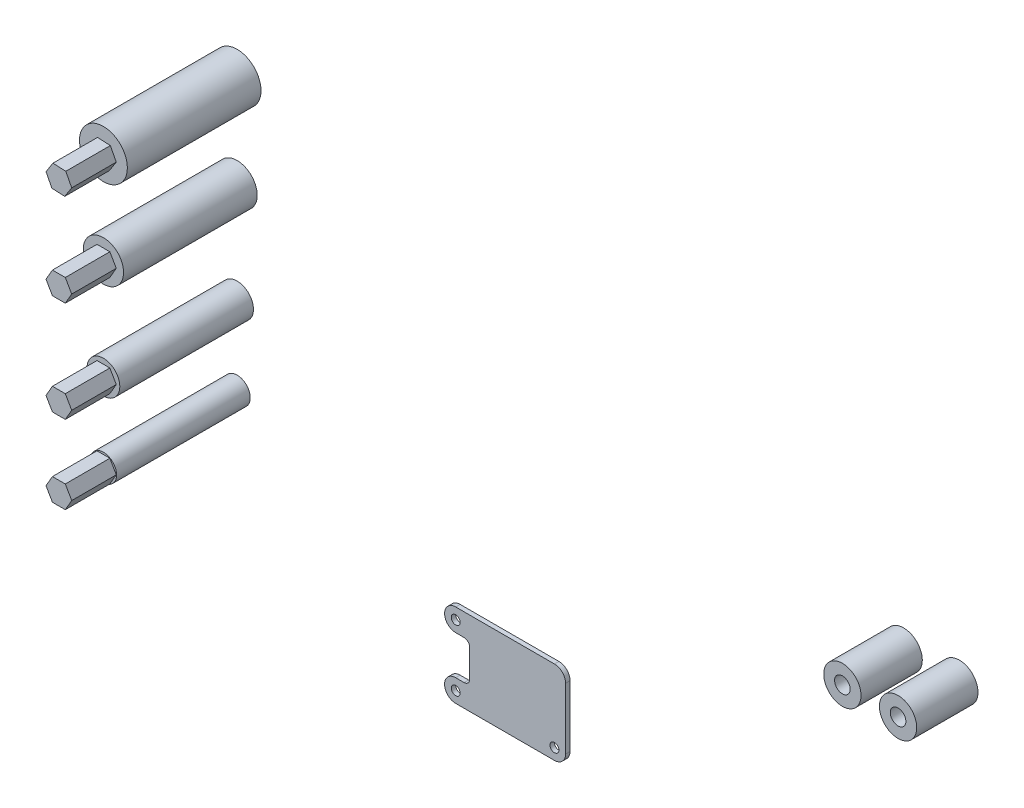
SolidWorks part; units mm, degrees
ref_plane "Front Plane" through (0, 0, 0) normal (0, 0, 1) x (1, 0, 0)
ref_plane "Top Plane" through (0, 0, 0) normal (0, 1, 0) x (1, 0, 0)
ref_plane "Right Plane" through (0, 0, 0) normal (1, 0, 0) x (0, 0, -1)
sketch "Sketch1" plane through (0, 0, 0) normal (0, 0, 1) x (1, 0, 0)
  line L0 (41.5252, 85.2495) -> (55.5016, 85.2495) construction
  line L1 (58.7537, 81.2495) -> (58.7537, 83.2495)
  line L2 (40.5252, 83.2495) -> (39.0252, 83.2495)
  line L3 (39.0252, 79.2495) -> (56.7537, 79.2495)
  line L4 (41.5252, 84.2495) -> (41.5252, 85.2495)
  line L5 (-0.0481, 105.8254) -> (0.9333, 107.5254)
  line L6 (0.9333, 107.5254) -> (-0.0481, 109.2254)
  line L7 (-0.0481, 109.2254) -> (-2.0111, 109.2254)
  line L8 (-2.0111, 109.2254) -> (-2.9926, 107.5254)
  line L9 (-2.9926, 107.5254) -> (-2.0111, 105.8254)
  line L10 (-2.0111, 105.8254) -> (-0.0481, 105.8254)
  line L11 (0.2405, 119.3642) -> (1.5107, 121.5642)
  line L12 (1.5107, 121.5642) -> (0.2405, 123.7642)
  line L13 (0.2405, 123.7642) -> (-2.2998, 123.7642)
  line L14 (-2.2998, 123.7642) -> (-3.57, 121.5642)
  line L15 (-3.57, 121.5642) -> (-2.2998, 119.3642)
  line L16 (-2.2998, 119.3642) -> (0.2405, 119.3642)
  line L17 (0.5292, 136.9341) -> (2.088, 139.6341)
  line L18 (2.088, 139.6341) -> (0.5292, 142.3341)
  line L19 (0.5292, 142.3341) -> (-2.5885, 142.3341)
  line L20 (-2.5885, 142.3341) -> (-4.1473, 139.6341)
  line L21 (-4.1473, 139.6341) -> (-2.5885, 136.9341)
  line L22 (-2.5885, 136.9341) -> (0.5292, 136.9341)
  line L23 (2.088, 139.6341) -> (2.588, 139.6341) construction
  line L24 (1.5107, 121.5642) -> (1.9107, 121.5642) construction
  line L25 (0.9333, 107.5254) -> (1.3333, 107.5254) construction
  line L26 (41.5252, 85.2495) -> (41.5252, 89.2495)
  line L27 (40.5252, 90.2495) -> (39.0252, 90.2495)
  line L28 (39.0252, 94.2495) -> (51.5016, 94.2495)
  line L29 (53.5016, 87.2495) -> (53.5016, 92.2495)
  line L30 (55.5016, 85.2495) -> (56.7537, 85.2495)
  line L31 (58.7537, 83.2495) -> (58.7537, 92.2495)
  line L32 (56.7537, 94.2495) -> (51.5016, 94.2495)
  line L33 (2.6654, 156.2509) -> (3.2654, 156.2509) construction
  line L34 (2.6654, 156.2509) -> (0.8179, 159.4509)
  line L35 (0.8179, 159.4509) -> (-2.8772, 159.4509)
  line L36 (-2.8772, 159.4509) -> (-4.7247, 156.2509)
  line L37 (-4.7247, 156.2509) -> (-2.8772, 153.0509)
  line L38 (-2.8772, 153.0509) -> (0.8179, 153.0509)
  line L39 (0.8179, 153.0509) -> (2.6654, 156.2509)
  circle A0 centre (39.0252, 81.2495) radius 2
  circle A1 centre (56.7537, 81.2495) radius 2
  circle A2 centre (39.0252, 81.2495) radius 0.8
  circle A3 centre (56.7537, 81.2495) radius 0.8
  arc A4 (58.7537, 92.2495) -> (56.7537, 94.2495) centre (56.7537, 92.2495) ccw
  arc A5 (40.5252, 83.2495) -> (41.5252, 84.2495) centre (40.5252, 84.2495) ccw
  circle A6 centre (-1.0296, 107.5254) radius 1.7 construction
  circle A7 centre (-1.0296, 121.5642) radius 2.2 construction
  circle A8 centre (-1.0296, 139.6341) radius 2.7 construction
  circle A9 centre (-1.0296, 107.5254) radius 2.363
  circle A10 centre (-1.0296, 121.5642) radius 2.9403
  circle A11 centre (-1.0296, 139.6341) radius 3.6177
  circle A12 centre (-1.0296, 139.6341) radius 1.5
  circle A13 centre (-1.0296, 121.5642) radius 1.25
  circle A14 centre (-1.0296, 107.5254) radius 1.05
  circle A15 centre (39.0252, 92.2495) radius 2
  circle A16 centre (39.0252, 92.2495) radius 0.8
  arc A17 (41.5252, 89.2495) -> (40.5252, 90.2495) centre (40.5252, 89.2495) ccw
  circle A18 centre (-1.0296, 156.2509) radius 3.2 construction
  circle A19 centre (-1.0296, 156.2509) radius 4.295
  circle A20 centre (-1.0296, 156.2509) radius 1.75
  circle B0 centre (78.6519, 127.0575) radius 1.4
  circle B1 centre (78.6519, 127.0575) radius 3.35
  circle B2 centre (78.736, 101.9939) radius 0.85
  circle B3 centre (78.736, 101.9939) radius 2.9
  circle B4 centre (78.736, 114.8621) radius 1.1
  circle B5 centre (78.736, 114.8621) radius 2.7
  circle B6 centre (88.6519, 127.0575) radius 1.4
  circle B7 centre (88.6519, 127.0575) radius 3.35
  circle B8 centre (98.6519, 127.0575) radius 1.4
  circle B9 centre (98.6519, 127.0575) radius 3.35
  circle B10 centre (108.6519, 127.0575) radius 1.4
  circle B11 centre (108.6519, 127.0575) radius 3.35
  circle B12 centre (118.6519, 127.0575) radius 1.4
  circle B13 centre (118.6519, 127.0575) radius 3.35
  circle B14 centre (128.6519, 127.0575) radius 1.4
  circle B15 centre (128.6519, 127.0575) radius 3.35
  circle B16 centre (88.736, 101.9939) radius 0.85
  circle B17 centre (88.736, 101.9939) radius 2.9
  circle B18 centre (98.736, 101.9939) radius 0.85
  circle B19 centre (98.736, 101.9939) radius 2.9
  circle B20 centre (108.736, 101.9939) radius 0.85
  circle B21 centre (108.736, 101.9939) radius 2.9
  circle B22 centre (88.736, 114.8621) radius 1.1
  circle B23 centre (88.736, 114.8621) radius 2.7
  circle B24 centre (76.8787, 139.9756) radius 1.6
  circle B25 centre (76.8787, 139.9756) radius 4
  circle B26 centre (86.8787, 139.9756) radius 1.6
  circle B27 centre (86.8787, 139.9756) radius 4
  dimension "D1" = 4
  dimension "D2" = 1.6
  dimension "D4" = 2
  dimension "D6" = 1
  dimension "D11" = 3
  dimension "D12" = 2.5
  dimension "D13" = 2.1
  dimension "D18" = 4
  dimension "D19" = 1.6
  dimension "D20" = 1
  dimension "D21" = 6.4
  dimension "D22" = 0.6
  dimension "D26" = 2
  dimension "D27" = 3.5
  dimension "D3" = 4
  dimension "D5" = 2.5
  dimension "D7" = 17.7284
  dimension "D8" = 3.4
  dimension "D9" = 5.4
  dimension "D10" = 4.4
  dimension "D14" = 0.5
  dimension "D15" = 0.4
  dimension "D16" = 0.4
  dimension "D17" = 11
  dimension "D23" = 6
  dimension "D24" = 4
  dimension "D25" = 2
sketch_block_instance "M2.5 spacer-10"
sketch_block "M2.5 spacer" parameters "D1"=2.8, "D3"=6.7, "D4"=2.7, "D2"=4.7
sketch_block_instance "M1.6 spacer-11"
sketch_block "M1.6 spacer" parameters "D1"=1.7, "D3"=5.8, "D4"=1.8, "D2"=3.8
sketch_block_instance "M2 spacer-4"
sketch_block "M2 spacer" parameters "D1"=2.2, "D3"=1, "D4"=2.2, "D2"=3.8
sketch_block_instance "M2.5 spacer-15"
sketch_block_instance "M2.5 spacer-16"
sketch_block_instance "M2.5 spacer-17"
sketch_block_instance "M2.5 spacer-18"
sketch_block_instance "M2.5 spacer-19"
sketch_block_instance "M1.6 spacer-14"
sketch_block_instance "M1.6 spacer-15"
sketch_block_instance "M1.6 spacer-16"
sketch_block_instance "M2 spacer-6"
sketch_block_instance "M3 spacer-1"
sketch_block "M3 spacer" parameters "D1"=3.2, "D2"=8, "D3"=5.6
sketch_block_instance "M3 spacer-2"
extrude "Boss-Extrude1" add sketch "Sketch1" along normal blind 8 contours A11 L22 L21 L20 L19 L18 L17 | A10 L16 L15 L14 L13 L12 L11 | A9 L10 L9 L8 L7 L6 L5 | A19 L39 L38 L37 L36 L35 L34 region at (-3.3258, 107.5254, 0) region at (-3.8868, 121.5642, 0) region at (-4.545, 139.6341, 0) region at (-5.2032, 156.2509, 0)
extrude "Boss-Extrude2" add sketch "Sketch1<3>" along normal blind 16 from surface contours L9 L10 L5 L6 L7 L8 A14 | A9 L10 L9 L8 L7 L6 L5 | A10 L16 L15 L14 L13 L12 L11 | L15 L16 L11 L12 L13 L14 A13 | A11 L22 L21 L20 L19 L18 L17 | L21 L22 L17 L18 L19 L20 A12 | A19 L39 L38 L37 L36 L35 L34 | L38 L39 L34 L35 L36 L37 A20 region at (-1.0296, 105.8773, 0) region at (-1.0296, 119.4314, 0) region at (-1.0296, 137.0166, 0) region at (1.657, 154.6998, 0) region at (-3.3258, 107.5254, 0) region at (-3.8868, 121.5642, 0) region at (-4.545, 139.6341, 0) region at (-5.2032, 156.2509, 0) starting at face at (-1.0296, 139.6341, 8)
sketch "Sketch1<3>" plane through (0, 0, 0) normal (0, 0, 1) x (1, 0, 0) same geometry as "Sketch1"
sketch "Sketch2" plane through (0, 0, 24) normal (0, 0, 1) x (1, 0, 0)
  circle A0 centre (-1.0296, 156.2509) radius 4.295 construction
  point P0 (-1.26, 156.2485)
  line B0 (0.1251, 137.6341) -> (1.2798, 139.6341)
  line B1 (1.2798, 139.6341) -> (0.1251, 141.6341)
  line B2 (0.1251, 141.6341) -> (-2.1843, 141.6341)
  line B3 (-2.1843, 141.6341) -> (-3.339, 139.6341)
  line B4 (-3.339, 139.6341) -> (-2.1843, 137.6341)
  line B5 (-2.1843, 137.6341) -> (0.1251, 137.6341)
  circle B6 centre (-1.0296, 139.6341) radius 2 construction
  line B7 (0.1251, 119.5642) -> (1.2798, 121.5642)
  line B8 (1.2798, 121.5642) -> (0.1251, 123.5642)
  line B9 (0.1251, 123.5642) -> (-2.1843, 123.5642)
  line B10 (-2.1843, 123.5642) -> (-3.339, 121.5642)
  line B11 (-3.339, 121.5642) -> (-2.1843, 119.5642)
  line B12 (-2.1843, 119.5642) -> (0.1251, 119.5642)
  circle B13 centre (-1.0296, 121.5642) radius 2 construction
  line B14 (0.1251, 105.5254) -> (1.2798, 107.5254)
  line B15 (1.2798, 107.5254) -> (0.1251, 109.5254)
  line B16 (0.1251, 109.5254) -> (-2.1843, 109.5254)
  line B17 (-2.1843, 109.5254) -> (-3.339, 107.5254)
  line B18 (-3.339, 107.5254) -> (-2.1843, 105.5254)
  line B19 (-2.1843, 105.5254) -> (0.1251, 105.5254)
  circle B20 centre (-1.0296, 107.5254) radius 2 construction
  line B21 (0.0317, 154.1998) -> (1.2773, 156.1444)
  line B22 (1.2773, 156.1444) -> (0.216, 158.1955)
  line B23 (0.216, 158.1955) -> (-2.0909, 158.302)
  line B24 (-2.0909, 158.302) -> (-3.3366, 156.3573)
  line B25 (-3.3366, 156.3573) -> (-2.2753, 154.3062)
  line B26 (-2.2753, 154.3062) -> (0.0317, 154.1998)
  circle B27 centre (-1.0296, 156.2509) radius 2 construction
sketch_block_instance "T4-hex-1"
sketch_block "T4-hex" parameters "D1"=4
sketch_block_instance "T4-hex-2"
sketch_block_instance "T4-hex-3"
sketch_block_instance "T4-hex-4"
extrude "Boss-Extrude3" add sketch "Sketch2" along normal blind 8
chamfer "Chamfer1" distance 1 angle 60 1 edges at (0.0204, 107.5254, 24) first distance on face at (0.0204, 107.5254, 24)
chamfer "Chamfer2" distance 1.2 angle 60 1 edges at (0.2204, 121.5642, 24) first distance on face at (0.2204, 121.5642, 24)
chamfer "Chamfer3" distance 1.4 angle 60 1 edges at (0.4704, 139.6341, 24) first distance on face at (0.4704, 139.6341, 24)
chamfer "Chamfer4" distance 1.6 angle 60 1 edges at (0.7204, 156.2509, 24) first distance on face at (0.7204, 156.2509, 24)
extrude "Boss-Extrude4" add sketch "Sketch1<5>" along normal blind 0.8 separate body contours L30 L29 L28 A15 L27 A17 L26 L4 A5 L2 A0 L3 A1 L1 | A0 A2 | A1 A3 | A15 A16 region at (49.468, 87.0237, 0) region at (58.1279, 79.8753, 0) region at (37.0818, 81.2495, 0) region at (40.3994, 93.6237, 0)
sketch "Sketch1<5>" plane through (0, 0, 0) normal (0, 0, 1) x (1, 0, 0) same geometry as "Sketch1"
extrude "Boss-Extrude5" add sketch "Sketch1<7>" along normal blind 11 separate body contours B15 B14 | B13 B12 region at (115.3966, 127.0575, 0) region at (125.3966, 127.0575, 0)
sketch "Sketch1<7>" plane through (0, 0, 0) normal (0, 0, 1) x (1, 0, 0) same geometry as "Sketch1"
